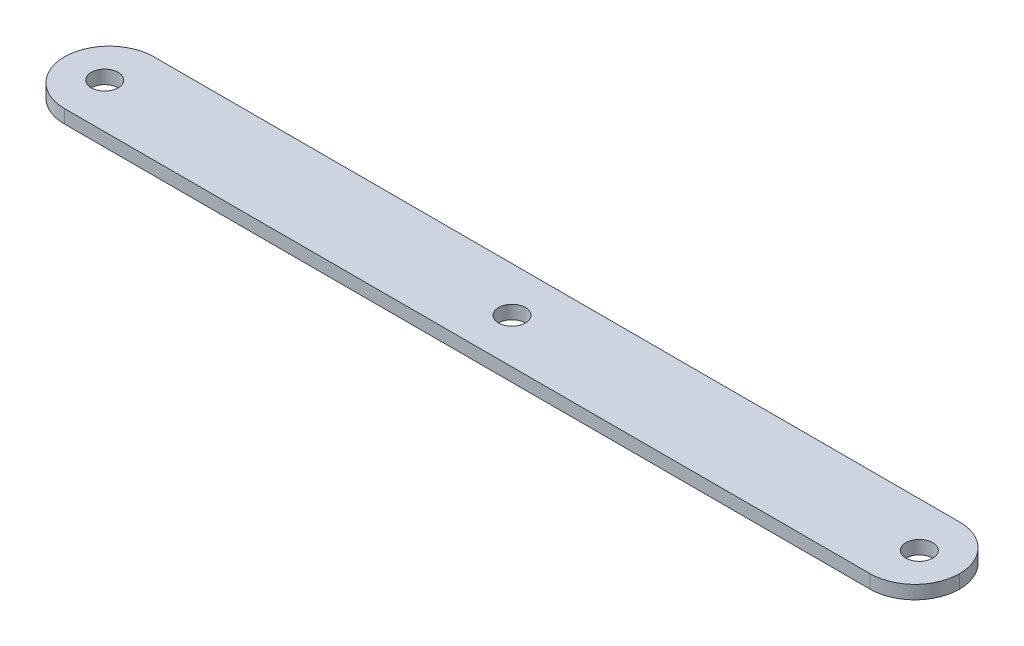
SolidWorks part; units mm, degrees
ref_plane "Front Plane" through (0, 0, 0) normal (0, 0, 1) x (1, 0, 0)
ref_plane "Top Plane" through (0, 0, 0) normal (0, 1, 0) x (1, 0, 0)
ref_plane "Right Plane" through (0, 0, 0) normal (1, 0, 0) x (0, 0, -1)
sketch "Sketch2" plane through (0, 0, 0) normal (0, 1, 0) x (1, 0, 0)
  line L1 (0, 0) -> (200, 0)
  line L2 (0, 0) -> (0, 20)
  line L3 (0, 20) -> (200, 20)
  line L4 (200, 0) -> (200, 20)
  dimension "D1" = 200
  dimension "D2" = 20
extrude "Boss-Extrude1" add sketch "Sketch2" along normal blind 3
sketch "Sketch3" plane through (0, 3, 0) normal (0, 1, 0) x (1, 0, 0)
  line L0 (200, 20) -> (0, 20) construction
  line L1 (0, 20) -> (0, 0) construction
  circle A0 centre (9, 10) radius 3
  dimension "D1" = 10
  dimension "D2" = 9
  dimension "D3" = 6
extrude "Cut-Extrude1" cut sketch "Sketch3" against normal through all
sketch "Sketch4" plane through (0, 3, 0) normal (0, 1, 0) x (1, 0, 0)
  line L0 (200, 20) -> (0, 20) construction
  line L1 (200, 0) -> (200, 20) construction
  circle A0 centre (191, 10) radius 3
  dimension "D1" = 10
  dimension "D3" = 6
  dimension "D2" = 9
extrude "Cut-Extrude2" cut sketch "Sketch4" against normal through all
fillet "Fillet1" radius 10 2 edges at (0, 1.5, -20) (0, 1.5, 0)
fillet "Fillet2" radius 10 2 edges at (200, 1.5, -20) (200, 1.5, 0)
sketch "Sketch6" plane through (0, 3, 0) normal (0, 1, 0) x (1, 0, 0)
  line L2 (190, 20) -> (10, 20) construction
  line L3 (10, 0) -> (190, 0) construction
  circle A0 centre (100, 10) radius 3
  dimension "D1" = 6
  dimension "D3" = 20
  dimension "D4" = 10
extrude "Cut-Extrude3" cut sketch "Sketch6" against normal through all
sketch "Sketch7" plane through (0, 3, 0) normal (0, 1, 0) x (1, 0, 0)
  line L0 (190, 20) -> (10, 20) construction
  line L1 (19, 15) -> (90, 15)
  line L2 (19, 15) -> (19, 5)
  line L3 (19, 5) -> (90, 5)
  line L4 (90, 15) -> (90, 5)
  line L5 (10, 0) -> (190, 0) construction
  line L7 (110, 15) -> (181, 15)
  line L8 (110, 15) -> (110, 5)
  line L9 (110, 5) -> (181, 5)
  line L10 (181, 15) -> (181, 5)
  circle A0 centre (9, 10) radius 3 construction
  circle A1 centre (100, 10) radius 3 construction
  circle A2 centre (191, 10) radius 3 construction
  dimension "D5" = 10
  dimension "D1" = 5
  dimension "D2" = 5
  dimension "D3" = 10
  dimension "D4" = 10
  dimension "D6" = 10
extrude "Cut-Extrude4" [suppressed] cut sketch "Sketch7" against normal blind 10
